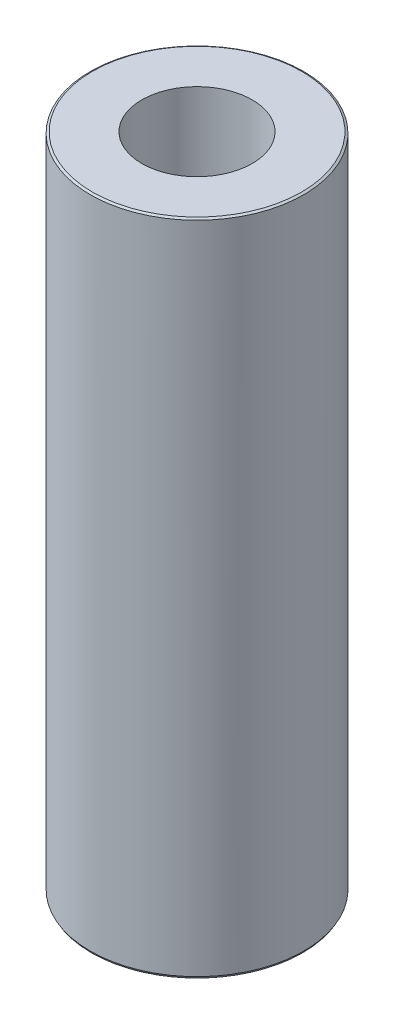
SolidWorks part; units mm, degrees
ref_plane "Front Plane" through (0, 0, 0) normal (0, 0, 1) x (1, 0, 0)
ref_plane "Top Plane" through (0, 0, 0) normal (0, 1, 0) x (1, 0, 0)
ref_plane "Right Plane" through (0, 0, 0) normal (1, 0, 0) x (0, 0, -1)
sketch "Sketch1" plane through (0, 0, 0) normal (0, 1, 0) x (1, 0, 0)
  circle A0 centre (0, 0) radius 20
  dimension "SHAFT_OD" = 40
extrude "Boss-Extrude1" add sketch "Sketch1" along normal blind 123.3566
sketch "Sketch2" plane through (0, 0, 0) normal (0, 1, 0) x (1, 0, 0)
  circle A0 centre (0, 0) radius 10.3449
  dimension "BORE_D" = 20.6898
extrude "Cut-Extrude1" cut sketch "Sketch2" along normal through all
chamfer "Chamfer1" distance 0.2311 angle 60 2 edges at (0, 123.3566, 20) (0, 0, 20) first distance on face at (0, 123.3566, 20) first distance on face at (0, 0, 10.3449)
